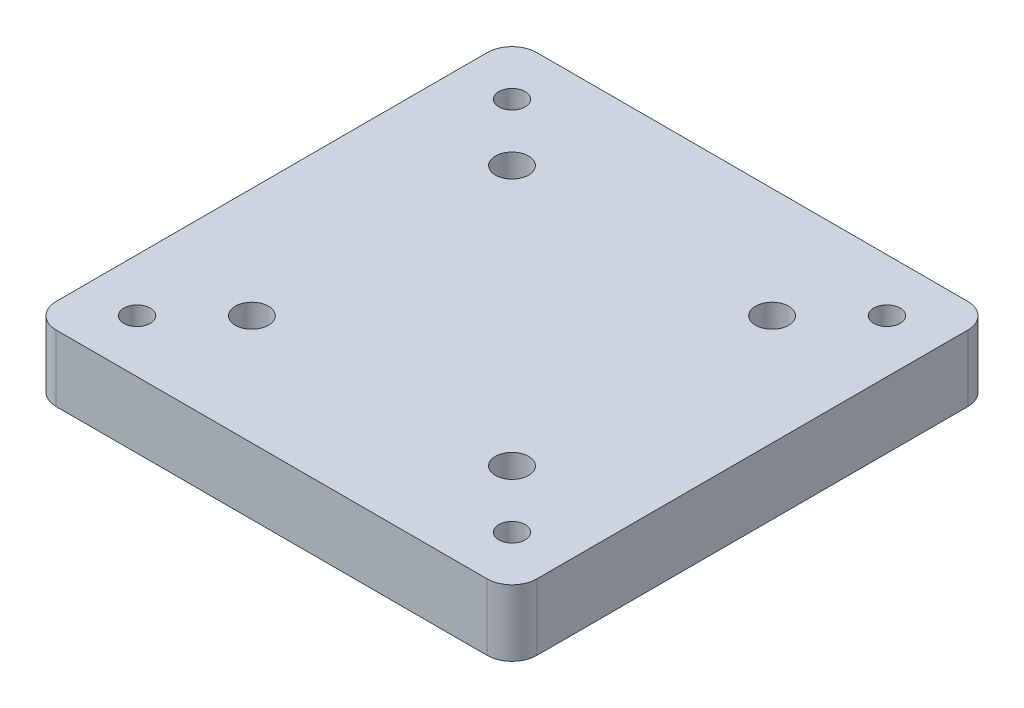
SolidWorks part; units mm, degrees
ref_plane "Płaszczyzna przednia" through (0, 0, 0) normal (0, 0, 1) x (1, 0, 0)
ref_plane "Płaszczyzna górna" through (0, 0, 0) normal (0, 1, 0) x (1, 0, 0)
ref_plane "Płaszczyzna prawa" through (0, 0, 0) normal (1, 0, 0) x (0, 0, -1)
sketch "Szkic2" plane through (0, 0, 0) normal (0, 1, 0) x (1, 0, 0)
  line L0 (-72.966, -6.6369) -> (-72.966, -51.8869) construction
  line L1 (-72.966, -6.6369) -> (-27.716, -6.6369) construction
  line L2 (-27.716, -6.6369) -> (-27.716, -51.8869) construction
  line L3 (-27.716, -51.8869) -> (-72.966, -51.8869) construction
  line L4 (-66.036, -13.5669) -> (-66.036, -44.9569) construction
  line L5 (-66.036, -44.9569) -> (-34.646, -44.9569) construction
  line L6 (-34.646, -44.9569) -> (-34.646, -13.5669) construction
  line L7 (-34.646, -13.5669) -> (-66.036, -13.5669) construction
  line L10 (-72.966, -6.6369) -> (-27.716, -51.8869) construction
  line L12 (-76.341, -58.2619) -> (-24.341, -58.2619)
  line L13 (-79.341, -55.2619) -> (-79.341, -3.2619)
  line L14 (-76.341, -0.2619) -> (-24.341, -0.2619)
  line L15 (-21.341, -55.2619) -> (-21.341, -3.2619)
  line L16 (-79.341, -58.2619) -> (-21.341, -0.2619) construction
  line L17 (-79.341, -0.2619) -> (-21.341, -58.2619) construction
  circle A0 centre (-72.966, -6.6369) radius 1.5987
  circle A1 centre (-27.716, -6.6369) radius 1.6
  circle A2 centre (-27.716, -51.8869) radius 1.5986
  circle A3 centre (-72.966, -51.8869) radius 1.6
  circle A4 centre (-34.646, -13.5669) radius 2
  circle A5 centre (-66.036, -13.5669) radius 2
  circle A6 centre (-66.036, -44.9569) radius 2
  circle A7 centre (-34.646, -44.9569) radius 2
  circle A8 centre (-66.036, -13.5669) radius 6
  circle A9 centre (-34.646, -13.5669) radius 6
  circle A10 centre (-66.036, -44.9569) radius 6
  circle A11 centre (-34.646, -44.9569) radius 6
  arc A12 (-76.341, -0.2619) -> (-79.341, -3.2619) centre (-76.341, -3.2619) ccw
  arc A13 (-21.341, -3.2619) -> (-24.341, -0.2619) centre (-24.341, -3.2619) ccw
  arc A14 (-21.341, -55.2619) -> (-24.341, -58.2619) centre (-24.341, -55.2619) cw
  arc A15 (-76.341, -58.2619) -> (-79.341, -55.2619) centre (-76.341, -55.2619) cw
  point P9 (-50.341, -29.2619)
  point P21 (-50.341, -29.2619)
  point P22 (-50.341, -29.2619)
  point P24 (-50.341, -29.2619)
  dimension "D1" = 3
  dimension "D2" = 3
  dimension "D3" = 3
  dimension "D4" = 3
extrude "Dodanie-wyciągnięcie1" add sketch "Szkic2" along normal blind 8 contours A15 L12 A14 L15 A13 L14 A12 L13 A11 A10 A9 A8 A3 A2 A1 A0 | A9 A4 | A8 A5 | A11 A7 | A10 A6 region at (-50.341, 0, 29.2619) region at (-71.8663, 0, 13.5669) region at (-40.4763, 0, 13.5669) region at (-71.8663, 0, 44.9569) region at (-40.4763, 0, 44.9569)
extrude "Dodanie-wyciągnięcie2" add sketch "Szkic2<3>" against normal blind 2 contours A7 | A6 | A5 | A4 | A11 | A10 | A8 | A9 region at (-34.646, 0, 13.5669) region at (-66.036, 0, 13.5669) region at (-66.036, 0, 44.9569) region at (-34.646, 0, 44.9569)
sketch "Szkic2<3>" plane through (0, 0, 0) normal (0, 1, 0) x (1, 0, 0) same geometry as "Szkic2"
